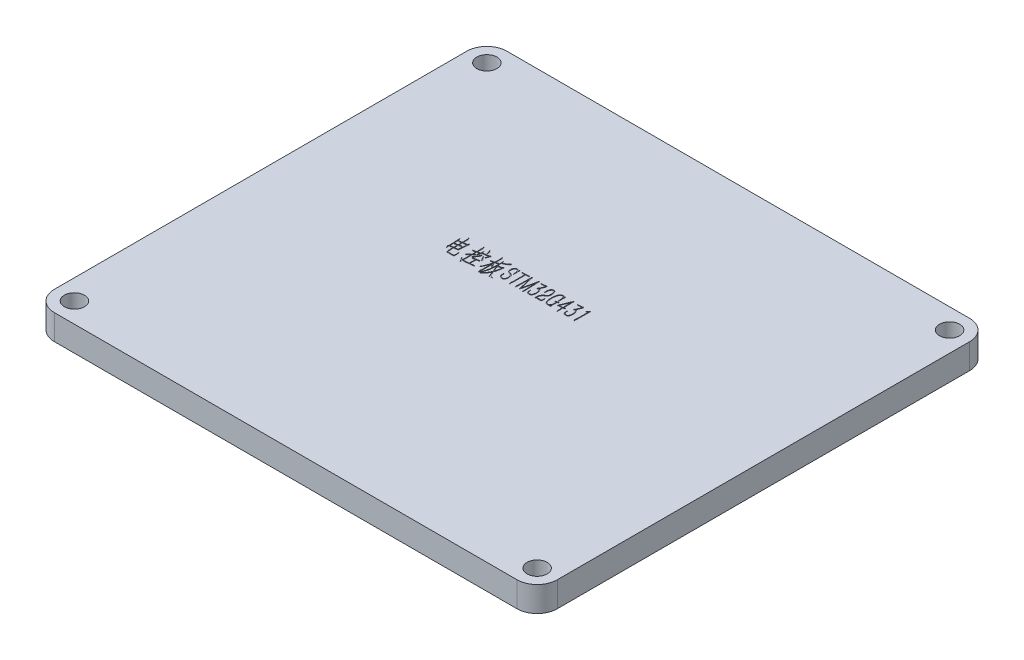
SolidWorks part; units mm, degrees
ref_plane "前视基准面" through (0, 0, 0) normal (0, 0, 1) x (1, 0, 0)
ref_plane "上视基准面" through (0, 0, 0) normal (0, 1, 0) x (1, 0, 0)
ref_plane "右视基准面" through (0, 0, 0) normal (1, 0, 0) x (0, 0, -1)
other "Configuration Table"
sketch "草图1" plane through (0, 0, 0) normal (0, 1, 0) x (1, 0, 0)
  line L1 (4, 0) -> (96, 0)
  line L2 (0, -4) -> (0, -86)
  line L3 (4, -90) -> (96, -90)
  line L4 (100, -4) -> (100, -86)
  arc A0 (0, -86) -> (4, -90) centre (4, -86) ccw
  arc A1 (96, -90) -> (100, -86) centre (96, -86) ccw
  arc A2 (96, 0) -> (100, -4) centre (96, -4) cw
  arc A3 (4, 0) -> (0, -4) centre (4, -4) ccw
  circle A4 centre (4, -4) radius 2
  circle A5 centre (96, -4) radius 2
  circle A6 centre (96, -86) radius 2
  circle A7 centre (4, -86) radius 2
  point P7 (0, -90)
  point P12 (100, 0)
  point P15 (0, 0)
  dimension "D3" = 4
  dimension "D4" = 4
  dimension "D5" = 4
  dimension "D6" = 4
  dimension "D7" = 4
  dimension "D1" = 100
  dimension "D2" = 90
extrude "凸台-拉伸2" add sketch "草图1" along normal blind 5
sketch "草图3" plane through (0, 5, 0) normal (0, 1, 0) x (1, 0, 0)
  text T0 "电控板STM32G431"
extrude "切除-拉伸1" cut sketch "草图3" against normal blind 0.1
